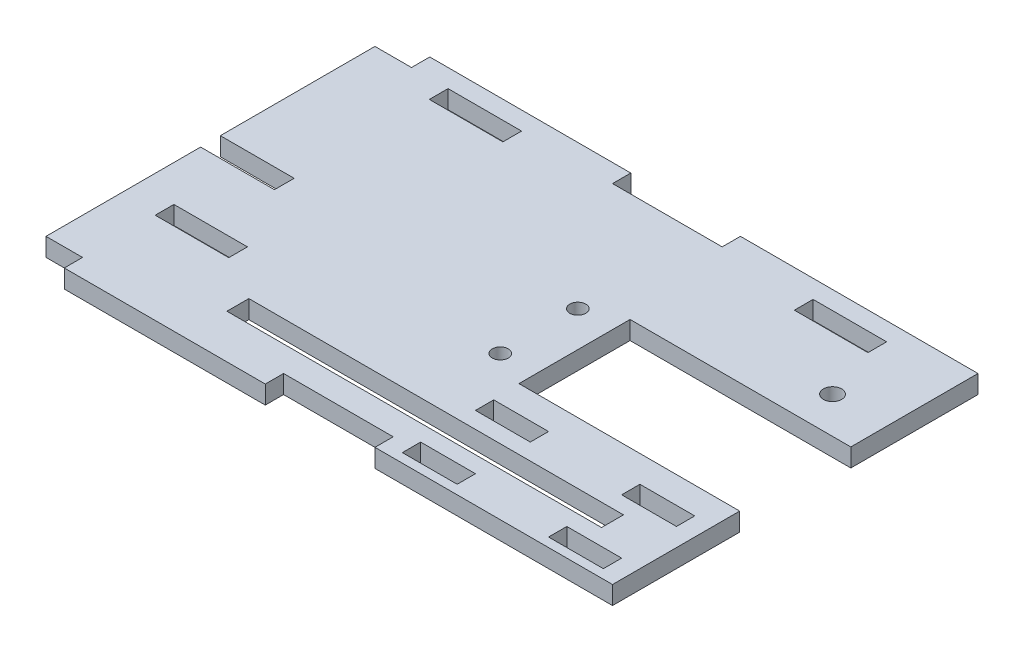
SolidWorks part; units mm, degrees
ref_plane "Front Plane" through (0, 0, 0) normal (0, 0, 1) x (1, 0, 0)
ref_plane "Top Plane" through (0, 0, 0) normal (0, 1, 0) x (1, 0, 0)
ref_plane "Right Plane" through (0, 0, 0) normal (1, 0, 0) x (0, 0, -1)
sketch "Sketch1" plane through (0, 0, 0) normal (0, 1, 0) x (1, 0, 0)
  line L0 (0, 63.5) -> (203.2, 63.5) construction
  line L1 (0, 0) -> (203.2, 0)
  line L2 (0, 0) -> (0, 60.071)
  line L3 (0, 127) -> (203.2, 127)
  line L4 (203.2, 0) -> (203.2, 44.196)
  line L5 (202.946, 82.55) -> (126.746, 82.55) construction
  line L7 (202.946, 44.45) -> (126.746, 44.45) construction
  line L8 (126.746, 82.55) -> (126.746, 44.45) construction
  line L9 (203.2, 82.804) -> (126.492, 82.804)
  line L10 (126.492, 82.804) -> (126.492, 44.196)
  line L11 (203.2, 44.196) -> (126.492, 44.196)
  line L12 (203.2, 60.579) -> (203.2, 53.721)
  line L13 (0, 66.929) -> (25.654, 66.929)
  line L14 (0, 66.675) -> (25.4, 66.675) construction
  line L16 (0, 60.325) -> (25.4, 60.325) construction
  line L17 (25.4, 66.675) -> (25.4, 60.325) construction
  line L22 (25.654, 66.929) -> (25.654, 60.071)
  line L23 (0, 60.071) -> (25.654, 60.071)
  line L27 (0, 66.929) -> (0, 127)
  line L28 (203.2, 82.804) -> (203.2, 127)
  line L29 (203.2, 53.721) -> (203.2, 60.579)
  line L30 (203.2, 82.804) -> (203.2, 44.196) construction
  line L31 (202.946, 82.55) -> (202.946, 44.45) construction
  dimension "D1" = 203.2
  dimension "D2" = 127
  dimension "D4" = 38.1
  dimension "D5" = 76.2
  dimension "D9" = 25.4
  dimension "D10" = 6.35
  dimension "D6" = 0.254
  dimension "D11" = 0.254
extrude "Boss-Extrude1" add sketch "Sketch1" along normal blind 6.35 contours L28 L3 L27 L13 L22 L23 L2 L1 L4 L11 L10 L9 region at (94.0263, 0, -63.5)
sketch "Sketch4" plane through (0, 6.35, 0) normal (0, 1, 0) x (1, 0, 0)
  line L1 (25.4762, 6.4262) -> (50.8762, 6.4262) construction
  line L2 (25.4762, 6.4262) -> (25.4762, 12.7762) construction
  line L3 (25.4762, 12.7762) -> (50.8762, 12.7762) construction
  line L4 (50.8762, 6.4262) -> (50.8762, 12.7762) construction
  line L6 (101.6, 0) -> (101.6, 127) construction
  line L8 (0, 63.5) -> (196.85, 63.5) construction
  line L9 (0, 66.929) -> (0, 60.071)
  line L16 (152.3238, 6.4262) -> (152.3238, 12.7762) construction
  line L17 (177.7238, 12.7762) -> (152.3238, 12.7762) construction
  line L18 (177.7238, 6.4262) -> (177.7238, 12.7762) construction
  line L19 (177.7238, 6.4262) -> (152.3238, 6.4262) construction
  line L20 (177.7238, 120.5738) -> (152.3238, 120.5738) construction
  line L21 (177.7238, 120.5738) -> (177.7238, 114.2238) construction
  line L22 (177.7238, 114.2238) -> (152.3238, 114.2238) construction
  line L23 (152.3238, 120.5738) -> (152.3238, 114.2238) construction
  line L24 (50.8762, 120.5738) -> (50.8762, 114.2238) construction
  line L25 (25.4762, 114.2238) -> (50.8762, 114.2238) construction
  line L26 (25.4762, 120.5738) -> (25.4762, 114.2238) construction
  line L27 (25.4762, 120.5738) -> (50.8762, 120.5738) construction
  line L28 (50.9524, 120.65) -> (50.9524, 114.1476)
  line L29 (25.4, 114.1476) -> (50.9524, 114.1476)
  line L30 (25.4, 120.65) -> (25.4, 114.1476)
  line L31 (25.4, 120.65) -> (50.9524, 120.65)
  line L32 (177.8, 120.65) -> (152.2476, 120.65)
  line L33 (152.2476, 120.65) -> (152.2476, 114.1476)
  line L34 (177.8, 114.1476) -> (152.2476, 114.1476)
  line L35 (177.8, 120.65) -> (177.8, 114.1476)
  line L36 (25.4, 6.35) -> (50.9524, 6.35) construction
  line L37 (50.9524, 6.35) -> (50.9524, 12.8524) construction
  line L38 (25.4, 12.8524) -> (50.9524, 12.8524) construction
  line L39 (25.4, 6.35) -> (25.4, 12.8524) construction
  line L40 (152.2476, 6.35) -> (152.2476, 12.8524) construction
  line L41 (177.8, 12.8524) -> (152.2476, 12.8524) construction
  line L42 (177.8, 6.35) -> (177.8, 12.8524) construction
  line L43 (177.8, 6.35) -> (152.2476, 6.35) construction
  line L44 (12.7, 127) -> (12.7, 120.65)
  line L45 (0, 0) -> (12.7, 0)
  line L46 (0, 0) -> (0, 6.35)
  line L47 (0, 6.35) -> (12.7, 6.35)
  line L48 (12.7, 0) -> (12.7, 6.35)
  line L49 (82.55, 0) -> (120.65, 0)
  line L50 (82.55, 0) -> (82.55, 6.35)
  line L51 (82.55, 6.35) -> (120.65, 6.35)
  line L52 (120.65, 0) -> (120.65, 6.35)
  line L53 (0, 120.65) -> (12.7, 120.65)
  line L54 (0, 127) -> (0, 120.65)
  line L55 (0, 127) -> (12.7, 127)
  line L56 (120.65, 127) -> (120.65, 120.65)
  line L57 (82.55, 120.65) -> (120.65, 120.65)
  line L58 (82.55, 127) -> (82.55, 120.65)
  line L59 (82.55, 127) -> (120.65, 127)
  line L60 (0, 66.929) -> (25.654, 66.929) construction
  line L61 (0, 60.071) -> (25.654, 60.071) construction
  line L62 (0, 0) -> (0, 60.071) construction
  line L63 (0, 0) -> (203.2, 0) construction
  dimension "D2" = 25.4
  dimension "D3" = 6.35
  dimension "D8" = 6.35
  dimension "D9" = 12.7
  dimension "D10" = 6.35
  dimension "D11" = 6.35
  dimension "D12" = 38.1
  dimension "D13" = 25.4
  dimension "D4" = 0.0762
  dimension "D5" = 0.0762
  dimension "D6" = 0.0762
  dimension "D7" = 0.0762
extrude "Cut-Extrude1" cut sketch "Sketch4" against normal through all contours L53 L44 | L31 L30 L29 L28 | L58 L57 L56 | L35 L32 L33 L34 | L43 L42 L41 L40 | L52 L51 L50 | L39 L36 L37 L38 | L48 L47 region at (38.1762, 6.35, -117.3988) region at (165.0238, 6.35, -117.3988) region at (6.35, 6.35, -123.825) region at (6.35, 6.35, -3.175) region at (101.6, 6.35, -3.175) region at (101.6, 6.35, -123.825)
sketch "Sketch5" plane through (0, 6.35, 0) normal (0, 1, 0) x (1, 0, 0)
  line L0 (203.2, 82.804) -> (126.492, 82.804) construction
  line L25 (203.2, 127) -> (120.65, 127)
  line L26 (120.65, 127) -> (120.65, 120.65)
  line L27 (120.65, 120.65) -> (82.55, 120.65)
  line L28 (82.55, 120.65) -> (82.55, 127)
  line L29 (82.55, 127) -> (12.7, 127)
  line L30 (12.7, 127) -> (12.7, 120.65)
  line L31 (12.7, 120.65) -> (0, 120.65)
  line L32 (0, 120.65) -> (0, 66.929)
  line L33 (0, 66.929) -> (25.654, 66.929)
  line L34 (25.654, 66.929) -> (25.654, 60.071)
  line L35 (25.654, 60.071) -> (0, 60.071)
  line L36 (0, 60.071) -> (0, 6.35)
  line L37 (0, 6.35) -> (12.7, 6.35)
  line L38 (12.7, 6.35) -> (12.7, 0)
  line L39 (12.7, 0) -> (82.55, 0)
  line L40 (82.55, 0) -> (82.55, 6.35)
  line L41 (82.55, 6.35) -> (120.65, 6.35)
  line L42 (120.65, 6.35) -> (120.65, 0)
  line L43 (120.65, 0) -> (203.2, 0)
  line L44 (203.2, 0) -> (203.2, 44.196)
  line L45 (203.2, 44.196) -> (126.492, 44.196)
  line L46 (126.492, 44.196) -> (126.492, 82.804)
  line L47 (126.492, 82.804) -> (203.2, 82.804)
  line L48 (203.2, 82.804) -> (203.2, 127)
  line L49 (203.2, 127) -> (120.65, 127) construction
  line L50 (120.65, 127) -> (120.65, 120.65) construction
  line L51 (120.65, 120.65) -> (82.55, 120.65) construction
  line L52 (82.55, 120.65) -> (82.55, 127) construction
  line L53 (82.55, 127) -> (12.7, 127) construction
  line L54 (12.7, 127) -> (12.7, 120.65) construction
  line L55 (12.7, 120.65) -> (0, 120.65) construction
  line L56 (0, 120.65) -> (0, 66.929) construction
  line L57 (0, 66.929) -> (25.654, 66.929) construction
  line L58 (25.654, 66.929) -> (25.654, 60.071) construction
  line L59 (25.654, 60.071) -> (0, 60.071) construction
  line L60 (0, 60.071) -> (0, 6.35) construction
  line L61 (0, 6.35) -> (12.7, 6.35) construction
  line L62 (12.7, 6.35) -> (12.7, 0) construction
  line L63 (12.7, 0) -> (82.55, 0) construction
  line L64 (82.55, 0) -> (82.55, 6.35) construction
  line L65 (82.55, 6.35) -> (120.65, 6.35) construction
  line L66 (120.65, 6.35) -> (120.65, 0) construction
  line L67 (120.65, 0) -> (203.2, 0) construction
  line L68 (203.2, 0) -> (203.2, 44.196) construction
  line L69 (203.2, 44.196) -> (126.492, 44.196) construction
  line L70 (126.492, 44.196) -> (126.492, 82.804) construction
  line L71 (126.492, 82.804) -> (203.2, 82.804) construction
  line L72 (203.2, 82.804) -> (203.2, 127) construction
  circle A0 centre (184.15, 95.504) radius 3.175
  dimension "D4" = 6.35
  dimension "D1" = 12.7
  dimension "D3" = 19.05
  dimension "D2" = 0
extrude "Cut-Extrude2" cut sketch "Sketch5" against normal through all
sketch "Sketch6" plane through (0, 0, 0) normal (0, -1, 0) x (1, 0, 0)
  line L0 (180.8055, 0) -> (180.8055, -127) construction
  line L1 (120.65, 0) -> (203.2, 0) construction
  line L2 (120.65, -127) -> (203.2, -127) construction
  line L3 (180.8055, -63.5) -> (71.8356, -63.5) construction
  circle A0 centre (114.173, -50.038) radius 2.7781
  circle A1 centre (114.173, -50.038) radius 2.54 construction
  circle A2 centre (114.173, -76.962) radius 2.7781
  dimension "D1" = 5.5562
extrude "Cut-Extrude3" cut sketch "Sketch6" against normal through all
sketch "Sketch7" plane through (0, 6.35, 0) normal (0, 1, 0) x (1, 0, 0)
  line L0 (0, 6.35) -> (0, 60.071) construction
  line L1 (12.7, 38.1) -> (38.1, 38.1) construction
  line L2 (12.7, 38.1) -> (12.7, 31.75) construction
  line L3 (12.7, 31.75) -> (38.1, 31.75) construction
  line L4 (38.1, 38.1) -> (38.1, 31.75) construction
  line L5 (0, 6.35) -> (12.7, 6.35) construction
  line L6 (12.6238, 38.1762) -> (38.1762, 38.1762)
  line L7 (38.1762, 38.1762) -> (38.1762, 31.6738)
  line L8 (12.6238, 31.6738) -> (38.1762, 31.6738)
  line L9 (12.6238, 38.1762) -> (12.6238, 31.6738)
  dimension "D1" = 6.35
  dimension "D2" = 25.4
  dimension "D3" = 12.7
  dimension "D4" = 25.4
  dimension "D5" = 0.0762
extrude "Cut-Extrude4" cut sketch "Sketch7" against normal through all
sketch "Sketch8" plane through (0, 0, 0) normal (0, -1, 0) x (1, 0, 0)
  line L0 (120.65, 0) -> (203.2, 0) construction
  line L1 (196.85, -3.175) -> (177.8, -3.175)
  line L2 (196.85, -3.175) -> (196.85, -9.525)
  line L3 (196.85, -9.525) -> (177.8, -9.525)
  line L4 (177.8, -3.175) -> (177.8, -9.525)
  line L5 (203.2, 0) -> (203.2, -44.196) construction
  line L6 (153.8168, -19.05) -> (177.8, -19.05) construction
  line L7 (177.8, -34.925) -> (177.8, -28.575)
  line L8 (196.85, -28.575) -> (177.8, -28.575)
  line L9 (196.85, -34.925) -> (196.85, -28.575)
  line L10 (196.85, -34.925) -> (177.8, -34.925)
  line L11 (161.925, -4.0278) -> (161.925, -32.1047) construction
  line L12 (127, -34.925) -> (146.05, -34.925)
  line L13 (127, -34.925) -> (127, -28.575)
  line L14 (127, -28.575) -> (146.05, -28.575)
  line L15 (146.05, -34.925) -> (146.05, -28.575)
  line L16 (146.05, -3.175) -> (146.05, -9.525)
  line L17 (127, -9.525) -> (146.05, -9.525)
  line L18 (127, -3.175) -> (127, -9.525)
  line L19 (127, -3.175) -> (146.05, -3.175)
  dimension "D1" = 3.175
  dimension "D2" = 6.35
  dimension "D3" = 6.35
  dimension "D4" = 19.05
  dimension "D5" = 9.525
  dimension "D6" = 31.75
extrude "Cut-Extrude5" cut sketch "Sketch8" against normal through all both and the other way through all
sketch "Sketch9" plane through (0, 0, 0) normal (0, -1, 0) x (1, 0, 0)
  line L1 (184.15, -15.24) -> (53.975, -15.24)
  line L2 (184.15, -15.24) -> (184.15, -22.86)
  line L3 (184.15, -22.86) -> (53.975, -22.86)
  line L4 (53.975, -15.24) -> (53.975, -22.86)
  line L5 (184.15, -19.05) -> (175.5768, -19.05) construction
  line L6 (196.85, -9.525) -> (177.8, -9.525) construction
  line L7 (177.8, -28.575) -> (196.85, -28.575) construction
  line L8 (196.85, -3.175) -> (196.85, -9.525) construction
  point P4 (189.9809, -15.24)
  dimension "D1" = 7.62
  dimension "D2" = 130.175
  dimension "D3" = 12.7
extrude "Cut-Extrude6" cut sketch "Sketch9" against normal through all both and the other way through all
